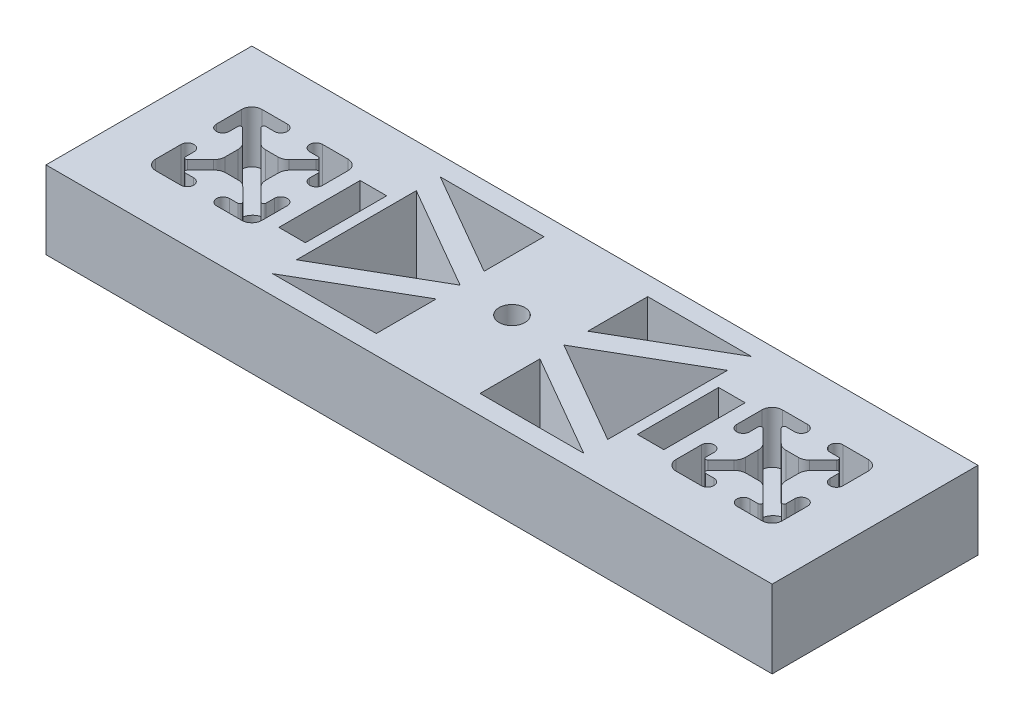
SolidWorks part; units mm, degrees
ref_plane "Front" through (0, 0, 0) normal (0, 0, 1) x (1, 0, 0)
ref_plane "Top" through (0, 0, 0) normal (0, 1, 0) x (1, 0, 0)
ref_plane "Right" through (0, 0, 0) normal (1, 0, 0) x (0, 0, -1)
sketch "Sketch1" plane through (0, 0, 0) normal (0, 1, 0) x (1, 0, 0)
  line L1 (0, 0) -> (177.8, 0)
  line L2 (0, 0) -> (0, 50.4)
  line L3 (0, 50.4) -> (177.8, 50.4)
  line L4 (177.8, 0) -> (177.8, 50.4)
  dimension "D1" = 177.8
  dimension "D2" = 50.4
extrude "Boss-Extrude1" add sketch "Sketch1" along normal blind 6.35
sketch "Sketch2" plane through (0, 6.35, 0) normal (0, 1, 0) x (1, 0, 0)
  line L0 (37.6996, 29.52) -> (37.6996, 35.7372) construction
  line L1 (35.7368, 37.7) -> (29.5196, 37.7) construction
  line L2 (29.5196, 35.56) -> (31.619, 35.56) construction
  line L3 (32.3326, 33.8353) -> (28.9966, 30.504) construction
  line L4 (26.7566, 29.5771) -> (23.643, 29.5771) construction
  line L5 (21.403, 30.504) -> (18.067, 33.8353) construction
  line L6 (18.7806, 35.56) -> (20.88, 35.56) construction
  line L7 (20.88, 37.7) -> (14.6628, 37.7) construction
  line L8 (12.7, 35.7372) -> (12.7, 29.52) construction
  line L9 (14.84, 29.52) -> (14.84, 31.5965) construction
  line L10 (16.5637, 32.3112) -> (19.7659, 29.1135) construction
  line L11 (20.743, 26.7568) -> (20.743, 23.6432) construction
  line L12 (19.7659, 21.2865) -> (16.5637, 18.0888) construction
  line L13 (14.84, 18.8035) -> (14.84, 20.88) construction
  line L14 (12.7, 20.88) -> (12.7, 14.6628) construction
  line L15 (14.6628, 12.7) -> (20.8121, 12.7) construction
  line L16 (20.8121, 14.84) -> (18.7806, 14.84) construction
  line L17 (18.067, 16.5647) -> (21.403, 19.896) construction
  line L18 (23.643, 20.8229) -> (26.7566, 20.8229) construction
  line L19 (28.9966, 19.896) -> (32.3326, 16.5647) construction
  line L20 (31.619, 14.84) -> (29.5875, 14.84) construction
  line L21 (29.5875, 12.7) -> (35.7368, 12.7) construction
  line L22 (37.6996, 14.6628) -> (37.6996, 20.88) construction
  line L23 (35.5596, 20.88) -> (35.5596, 18.8035) construction
  line L24 (33.8359, 18.0888) -> (30.6337, 21.2865) construction
  line L25 (29.6566, 23.6432) -> (29.6566, 26.7568) construction
  line L26 (30.6337, 29.1135) -> (33.8359, 32.3112) construction
  line L27 (35.5596, 31.5965) -> (35.5596, 29.52) construction
  line L28 (0, 50.4) -> (0, 0) construction
  line L29 (177.8, 50.4) -> (0, 50.4) construction
  line L30 (0, 0) -> (177.8, 0) construction
  line L31 (88.9, 50.4) -> (88.9, 0) construction
  line L32 (142.2404, 31.5965) -> (142.2404, 29.52) construction
  line L33 (147.1663, 29.1135) -> (143.9641, 32.3112) construction
  line L34 (148.1434, 23.6432) -> (148.1434, 26.7568) construction
  line L35 (143.9641, 18.0888) -> (147.1663, 21.2865) construction
  line L36 (142.2404, 20.88) -> (142.2404, 18.8035) construction
  line L37 (140.1004, 14.6628) -> (140.1004, 20.88) construction
  line L38 (148.2125, 12.7) -> (142.0632, 12.7) construction
  line L39 (146.181, 14.84) -> (148.2125, 14.84) construction
  line L40 (148.8034, 19.896) -> (145.4674, 16.5647) construction
  line L41 (154.157, 20.8229) -> (151.0434, 20.8229) construction
  line L42 (159.733, 16.5647) -> (156.397, 19.896) construction
  line L43 (156.9879, 14.84) -> (159.0194, 14.84) construction
  line L44 (163.1372, 12.7) -> (156.9879, 12.7) construction
  line L45 (165.1, 20.88) -> (165.1, 14.6628) construction
  line L46 (162.96, 18.8035) -> (162.96, 20.88) construction
  line L47 (158.0341, 21.2865) -> (161.2363, 18.0888) construction
  line L48 (157.057, 26.7568) -> (157.057, 23.6432) construction
  line L49 (161.2363, 32.3112) -> (158.0341, 29.1135) construction
  line L50 (162.96, 29.52) -> (162.96, 31.5965) construction
  line L51 (165.1, 35.7372) -> (165.1, 29.52) construction
  line L52 (156.92, 37.7) -> (163.1372, 37.7) construction
  line L53 (159.0194, 35.56) -> (156.92, 35.56) construction
  line L54 (156.397, 30.504) -> (159.733, 33.8353) construction
  line L55 (151.0434, 29.5771) -> (154.157, 29.5771) construction
  line L56 (145.4674, 33.8353) -> (148.8034, 30.504) construction
  line L57 (148.2804, 35.56) -> (146.181, 35.56) construction
  line L58 (142.0632, 37.7) -> (148.2804, 37.7) construction
  line L59 (140.1004, 29.52) -> (140.1004, 35.7372) construction
  line L60 (38.2076, 29.52) -> (38.2076, 35.7372)
  line L62 (0, 50.4) -> (0, 0)
  line L63 (0, 0) -> (177.8, 0)
  line L64 (177.8, 50.4) -> (177.8, 0)
  line L65 (35.7368, 38.208) -> (29.5196, 38.208)
  line L66 (29.5196, 35.052) -> (31.619, 35.052)
  line L67 (31.9737, 34.1948) -> (28.6376, 30.8635)
  line L68 (26.7566, 30.0851) -> (23.643, 30.0851)
  line L69 (21.762, 30.8635) -> (18.4259, 34.1948)
  line L70 (18.7806, 35.052) -> (20.88, 35.052)
  line L71 (20.88, 38.208) -> (14.6628, 38.208)
  line L72 (12.192, 35.7372) -> (12.192, 29.52)
  line L73 (15.348, 29.52) -> (15.348, 31.5965)
  line L74 (16.2047, 31.9517) -> (19.4069, 28.7541)
  line L75 (20.235, 26.7568) -> (20.235, 23.6432)
  line L76 (19.4069, 21.6459) -> (16.2047, 18.4483)
  line L77 (15.348, 18.8035) -> (15.348, 20.88)
  line L78 (12.192, 20.88) -> (12.192, 14.6628)
  line L79 (14.6628, 12.192) -> (20.8121, 12.192)
  line L80 (20.8121, 15.348) -> (18.7806, 15.348)
  line L81 (18.4259, 16.2052) -> (21.762, 19.5365)
  line L82 (23.643, 20.3149) -> (26.7566, 20.3149)
  line L83 (28.6376, 19.5365) -> (31.9737, 16.2052)
  line L84 (31.619, 15.348) -> (29.5875, 15.348)
  line L85 (29.5875, 12.192) -> (35.7368, 12.192)
  line L86 (38.2076, 14.6628) -> (38.2076, 20.88)
  line L87 (35.0516, 20.88) -> (35.0516, 18.8035)
  line L88 (34.1949, 18.4483) -> (30.9927, 21.6459)
  line L89 (30.1646, 23.6432) -> (30.1646, 26.7568)
  line L90 (30.9927, 28.7541) -> (34.1949, 31.9517)
  line L91 (35.0516, 31.5965) -> (35.0516, 29.52)
  line L92 (142.7484, 31.5965) -> (142.7484, 29.52)
  line L93 (139.5924, 29.52) -> (139.5924, 35.7372)
  line L94 (142.0632, 38.208) -> (148.2804, 38.208)
  line L95 (148.2804, 35.052) -> (146.181, 35.052)
  line L96 (145.8263, 34.1948) -> (149.1624, 30.8635)
  line L97 (151.0434, 30.0851) -> (154.157, 30.0851)
  line L98 (156.038, 30.8635) -> (159.3741, 34.1948)
  line L99 (159.0194, 35.052) -> (156.92, 35.052)
  line L100 (156.92, 38.208) -> (163.1372, 38.208)
  line L101 (165.608, 35.7372) -> (165.608, 29.52)
  line L102 (162.452, 29.52) -> (162.452, 31.5965)
  line L103 (161.5953, 31.9517) -> (158.3931, 28.7541)
  line L104 (157.565, 26.7568) -> (157.565, 23.6432)
  line L105 (158.3931, 21.6459) -> (161.5953, 18.4483)
  line L106 (162.452, 18.8035) -> (162.452, 20.88)
  line L107 (165.608, 20.88) -> (165.608, 14.6628)
  line L108 (163.1372, 12.192) -> (156.9879, 12.192)
  line L109 (156.9879, 15.348) -> (159.0194, 15.348)
  line L110 (159.3741, 16.2052) -> (156.038, 19.5365)
  line L111 (154.157, 20.3149) -> (151.0434, 20.3149)
  line L112 (149.1624, 19.5365) -> (145.8263, 16.2052)
  line L113 (146.181, 15.348) -> (148.2125, 15.348)
  line L114 (148.2125, 12.192) -> (142.0632, 12.192)
  line L115 (139.5924, 14.6628) -> (139.5924, 20.88)
  line L116 (142.7484, 20.88) -> (142.7484, 18.8035)
  line L117 (143.6051, 18.4483) -> (146.8073, 21.6459)
  line L118 (147.6354, 23.6432) -> (147.6354, 26.7568)
  line L119 (146.8073, 28.7541) -> (143.6051, 31.9517)
  line L120 (177.8, 50.4) -> (0, 50.4)
  arc A1 (37.6996, 35.7372) -> (35.7368, 37.7) centre (35.7368, 35.7372) ccw construction
  arc A2 (29.5196, 37.7) -> (29.5196, 35.56) centre (29.5196, 36.63) ccw construction
  arc A3 (31.619, 35.56) -> (32.3326, 33.8353) centre (31.619, 34.55) cw construction
  arc A4 (28.9966, 30.504) -> (26.7566, 29.5771) centre (26.7566, 32.7471) cw construction
  arc A5 (23.643, 29.5771) -> (21.403, 30.504) centre (23.643, 32.7471) cw construction
  arc A6 (18.067, 33.8353) -> (18.7806, 35.56) centre (18.7806, 34.55) cw construction
  arc A7 (20.88, 35.56) -> (20.88, 37.7) centre (20.88, 36.63) ccw construction
  arc A8 (14.6628, 37.7) -> (12.7, 35.7372) centre (14.6628, 35.7372) ccw construction
  arc A9 (12.7, 29.52) -> (14.84, 29.52) centre (13.77, 29.52) ccw construction
  arc A10 (14.84, 31.5965) -> (16.5637, 32.3112) centre (15.85, 31.5965) cw construction
  arc A11 (19.7659, 29.1135) -> (20.743, 26.7568) centre (17.4126, 26.7568) cw construction
  arc A12 (20.743, 23.6432) -> (19.7659, 21.2865) centre (17.4126, 23.6432) cw construction
  arc A13 (16.5637, 18.0888) -> (14.84, 18.8035) centre (15.85, 18.8035) cw construction
  arc A14 (14.84, 20.88) -> (12.7, 20.88) centre (13.77, 20.88) ccw construction
  arc A15 (12.7, 14.6628) -> (14.6628, 12.7) centre (14.6628, 14.6628) ccw construction
  arc A16 (20.8121, 12.7) -> (20.8121, 14.84) centre (20.8121, 13.77) ccw construction
  arc A17 (18.7806, 14.84) -> (18.067, 16.5647) centre (18.7806, 15.85) cw construction
  arc A18 (21.403, 19.896) -> (23.643, 20.8229) centre (23.643, 17.6529) cw construction
  arc A19 (26.7566, 20.8229) -> (28.9966, 19.896) centre (26.7566, 17.6529) cw construction
  arc A20 (32.3326, 16.5647) -> (31.619, 14.84) centre (31.619, 15.85) cw construction
  arc A21 (29.5875, 14.84) -> (29.5875, 12.7) centre (29.5875, 13.77) ccw construction
  arc A22 (35.7368, 12.7) -> (37.6996, 14.6628) centre (35.7368, 14.6628) ccw construction
  arc A23 (37.6996, 20.88) -> (35.5596, 20.88) centre (36.6296, 20.88) ccw construction
  arc A24 (35.5596, 18.8035) -> (33.8359, 18.0888) centre (34.5496, 18.8035) cw construction
  arc A25 (30.6337, 21.2865) -> (29.6566, 23.6432) centre (32.987, 23.6432) cw construction
  arc A26 (29.6566, 26.7568) -> (30.6337, 29.1135) centre (32.987, 26.7568) cw construction
  arc A27 (33.8359, 32.3112) -> (35.5596, 31.5965) centre (34.5496, 31.5965) cw construction
  arc A28 (35.5596, 29.52) -> (37.6996, 29.52) centre (36.6296, 29.52) ccw construction
  arc A29 (142.2404, 29.52) -> (140.1004, 29.52) centre (141.1704, 29.52) cw construction
  arc A30 (143.9641, 32.3112) -> (142.2404, 31.5965) centre (143.2504, 31.5965) ccw construction
  arc A31 (148.1434, 26.7568) -> (147.1663, 29.1135) centre (144.813, 26.7568) ccw construction
  arc A32 (147.1663, 21.2865) -> (148.1434, 23.6432) centre (144.813, 23.6432) ccw construction
  arc A33 (142.2404, 18.8035) -> (143.9641, 18.0888) centre (143.2504, 18.8035) ccw construction
  arc A34 (140.1004, 20.88) -> (142.2404, 20.88) centre (141.1704, 20.88) cw construction
  arc A35 (142.0632, 12.7) -> (140.1004, 14.6628) centre (142.0632, 14.6628) cw construction
  arc A36 (148.2125, 14.84) -> (148.2125, 12.7) centre (148.2125, 13.77) cw construction
  arc A37 (145.4674, 16.5647) -> (146.181, 14.84) centre (146.181, 15.85) ccw construction
  arc A38 (151.0434, 20.8229) -> (148.8034, 19.896) centre (151.0434, 17.6529) ccw construction
  arc A39 (156.397, 19.896) -> (154.157, 20.8229) centre (154.157, 17.6529) ccw construction
  arc A40 (159.0194, 14.84) -> (159.733, 16.5647) centre (159.0194, 15.85) ccw construction
  arc A41 (156.9879, 12.7) -> (156.9879, 14.84) centre (156.9879, 13.77) cw construction
  arc A42 (165.1, 14.6628) -> (163.1372, 12.7) centre (163.1372, 14.6628) cw construction
  arc A43 (162.96, 20.88) -> (165.1, 20.88) centre (164.03, 20.88) cw construction
  arc A44 (161.2363, 18.0888) -> (162.96, 18.8035) centre (161.95, 18.8035) ccw construction
  arc A45 (157.057, 23.6432) -> (158.0341, 21.2865) centre (160.3874, 23.6432) ccw construction
  arc A46 (158.0341, 29.1135) -> (157.057, 26.7568) centre (160.3874, 26.7568) ccw construction
  arc A47 (162.96, 31.5965) -> (161.2363, 32.3112) centre (161.95, 31.5965) ccw construction
  arc A48 (165.1, 29.52) -> (162.96, 29.52) centre (164.03, 29.52) cw construction
  arc A49 (163.1372, 37.7) -> (165.1, 35.7372) centre (163.1372, 35.7372) cw construction
  arc A50 (156.92, 35.56) -> (156.92, 37.7) centre (156.92, 36.63) cw construction
  arc A51 (159.733, 33.8353) -> (159.0194, 35.56) centre (159.0194, 34.55) ccw construction
  arc A52 (154.157, 29.5771) -> (156.397, 30.504) centre (154.157, 32.7471) ccw construction
  arc A53 (148.8034, 30.504) -> (151.0434, 29.5771) centre (151.0434, 32.7471) ccw construction
  arc A54 (146.181, 35.56) -> (145.4674, 33.8353) centre (146.181, 34.55) ccw construction
  arc A55 (148.2804, 37.7) -> (148.2804, 35.56) centre (148.2804, 36.63) cw construction
  arc A56 (140.1004, 35.7372) -> (142.0632, 37.7) centre (142.0632, 35.7372) cw construction
  arc A58 (38.2076, 35.7372) -> (35.7368, 38.208) centre (35.7368, 35.7372) ccw
  arc A59 (29.5196, 38.208) -> (29.5196, 35.052) centre (29.5196, 36.63) ccw
  arc A60 (31.619, 35.052) -> (31.9737, 34.1948) centre (31.619, 34.55) cw
  arc A61 (28.6376, 30.8635) -> (26.7566, 30.0851) centre (26.7566, 32.7471) cw
  arc A62 (23.643, 30.0851) -> (21.762, 30.8635) centre (23.643, 32.7471) cw
  arc A63 (18.4259, 34.1948) -> (18.7806, 35.052) centre (18.7806, 34.55) cw
  arc A64 (20.88, 35.052) -> (20.88, 38.208) centre (20.88, 36.63) ccw
  arc A65 (14.6628, 38.208) -> (12.192, 35.7372) centre (14.6628, 35.7372) ccw
  arc A66 (12.192, 29.52) -> (15.348, 29.52) centre (13.77, 29.52) ccw
  arc A67 (15.348, 31.5965) -> (16.2047, 31.9517) centre (15.85, 31.5965) cw
  arc A68 (19.4069, 28.7541) -> (20.235, 26.7568) centre (17.4126, 26.7568) cw
  arc A69 (20.235, 23.6432) -> (19.4069, 21.6459) centre (17.4126, 23.6432) cw
  arc A70 (16.2047, 18.4483) -> (15.348, 18.8035) centre (15.85, 18.8035) cw
  arc A71 (15.348, 20.88) -> (12.192, 20.88) centre (13.77, 20.88) ccw
  arc A72 (12.192, 14.6628) -> (14.6628, 12.192) centre (14.6628, 14.6628) ccw
  arc A73 (20.8121, 12.192) -> (20.8121, 15.348) centre (20.8121, 13.77) ccw
  arc A74 (18.7806, 15.348) -> (18.4259, 16.2052) centre (18.7806, 15.85) cw
  arc A75 (21.762, 19.5365) -> (23.643, 20.3149) centre (23.643, 17.6529) cw
  arc A76 (26.7566, 20.3149) -> (28.6376, 19.5365) centre (26.7566, 17.6529) cw
  arc A77 (31.9737, 16.2052) -> (31.619, 15.348) centre (31.619, 15.85) cw
  arc A78 (29.5875, 15.348) -> (29.5875, 12.192) centre (29.5875, 13.77) ccw
  arc A79 (35.7368, 12.192) -> (38.2076, 14.6628) centre (35.7368, 14.6628) ccw
  arc A80 (38.2076, 20.88) -> (35.0516, 20.88) centre (36.6296, 20.88) ccw
  arc A81 (35.0516, 18.8035) -> (34.1949, 18.4483) centre (34.5496, 18.8035) cw
  arc A82 (30.9927, 21.6459) -> (30.1646, 23.6432) centre (32.987, 23.6432) cw
  arc A83 (30.1646, 26.7568) -> (30.9927, 28.7541) centre (32.987, 26.7568) cw
  arc A84 (34.1949, 31.9517) -> (35.0516, 31.5965) centre (34.5496, 31.5965) cw
  arc A85 (35.0516, 29.52) -> (38.2076, 29.52) centre (36.6296, 29.52) ccw
  arc A86 (142.7484, 29.52) -> (139.5924, 29.52) centre (141.1704, 29.52) cw
  arc A87 (139.5924, 35.7372) -> (142.0632, 38.208) centre (142.0632, 35.7372) cw
  arc A88 (148.2804, 38.208) -> (148.2804, 35.052) centre (148.2804, 36.63) cw
  arc A89 (146.181, 35.052) -> (145.8263, 34.1948) centre (146.181, 34.55) ccw
  arc A90 (149.1624, 30.8635) -> (151.0434, 30.0851) centre (151.0434, 32.7471) ccw
  arc A91 (154.157, 30.0851) -> (156.038, 30.8635) centre (154.157, 32.7471) ccw
  arc A92 (159.3741, 34.1948) -> (159.0194, 35.052) centre (159.0194, 34.55) ccw
  arc A93 (156.92, 35.052) -> (156.92, 38.208) centre (156.92, 36.63) cw
  arc A94 (163.1372, 38.208) -> (165.608, 35.7372) centre (163.1372, 35.7372) cw
  arc A95 (165.608, 29.52) -> (162.452, 29.52) centre (164.03, 29.52) cw
  arc A96 (162.452, 31.5965) -> (161.5953, 31.9517) centre (161.95, 31.5965) ccw
  arc A97 (158.3931, 28.7541) -> (157.565, 26.7568) centre (160.3874, 26.7568) ccw
  arc A98 (157.565, 23.6432) -> (158.3931, 21.6459) centre (160.3874, 23.6432) ccw
  arc A99 (161.5953, 18.4483) -> (162.452, 18.8035) centre (161.95, 18.8035) ccw
  arc A100 (162.452, 20.88) -> (165.608, 20.88) centre (164.03, 20.88) cw
  arc A101 (165.608, 14.6628) -> (163.1372, 12.192) centre (163.1372, 14.6628) cw
  arc A102 (156.9879, 12.192) -> (156.9879, 15.348) centre (156.9879, 13.77) cw
  arc A103 (159.0194, 15.348) -> (159.3741, 16.2052) centre (159.0194, 15.85) ccw
  arc A104 (156.038, 19.5365) -> (154.157, 20.3149) centre (154.157, 17.6529) ccw
  arc A105 (151.0434, 20.3149) -> (149.1624, 19.5365) centre (151.0434, 17.6529) ccw
  arc A106 (145.8263, 16.2052) -> (146.181, 15.348) centre (146.181, 15.85) ccw
  arc A107 (148.2125, 15.348) -> (148.2125, 12.192) centre (148.2125, 13.77) cw
  arc A108 (142.0632, 12.192) -> (139.5924, 14.6628) centre (142.0632, 14.6628) cw
  arc A109 (139.5924, 20.88) -> (142.7484, 20.88) centre (141.1704, 20.88) cw
  arc A110 (142.7484, 18.8035) -> (143.6051, 18.4483) centre (143.2504, 18.8035) ccw
  arc A111 (146.8073, 21.6459) -> (147.6354, 23.6432) centre (144.813, 23.6432) ccw
  arc A112 (147.6354, 26.7568) -> (146.8073, 28.7541) centre (144.813, 26.7568) ccw
  arc A113 (143.6051, 31.9517) -> (142.7484, 31.5965) centre (143.2504, 31.5965) ccw
  dimension "D2" = 1.07
  dimension "D3" = 3.17
  dimension "D4" = 3.3305
  dimension "D8" = 1.9628
  dimension "D9" = 1.01
  dimension "D5" = 12.7
  dimension "D6" = 12.7
  dimension "D7" = 12.7
  dimension "D10" = 16.5637
  dimension "D12" = 0.508
  dimension "D13" = 0.508
extrude "Boss-Extrude2" add sketch "Sketch2" along normal blind 12.7
sketch "Sketch3" plane through (0, 19.05, 0) normal (0, 1, 0) x (1, 0, 0)
  line L0 (177.8, 50.4) -> (0, 50.4) construction
  line L1 (0, 50.4) -> (0, 0) construction
  circle A0 centre (88.9, 25.2) radius 3.175
  point P4 (88.9, 50.4)
  point P7 (0, 25.2)
  dimension "D1" = 6.35
extrude "Cut-Extrude1" cut sketch "Sketch3" against normal blind 10.16
sketch "Sketch4" plane through (0, 19.05, 0) normal (0, 1, 0) x (1, 0, 0)
  line L0 (50.8, 45.7306) -> (76.2, 45.7306)
  line L1 (76.2, 45.7306) -> (76.2, 31.0659)
  line L2 (76.2, 31.0659) -> (50.8, 45.7306)
  line L3 (76.2, 19.3341) -> (76.2, 4.6694)
  line L4 (76.2, 4.6694) -> (50.8, 4.6694)
  line L5 (50.8, 4.6694) -> (76.2, 19.3341)
  line L6 (50.8, 39.8647) -> (50.8, 10.5353)
  line L7 (50.8, 10.5353) -> (76.2, 25.2)
  line L8 (76.2, 25.2) -> (50.8, 39.8647)
  line L9 (0, 50.4) -> (0, 0) construction
  line L10 (88.9, 50.4) -> (88.9, 0) construction
  line L11 (177.8, 50.4) -> (0, 50.4) construction
  line L12 (0, 0) -> (177.8, 0) construction
  line L13 (101.6, 25.2) -> (127, 39.8647)
  line L14 (127, 10.5353) -> (101.6, 25.2)
  line L15 (127, 39.8647) -> (127, 10.5353)
  line L16 (127, 4.6694) -> (101.6, 19.3341)
  line L17 (101.6, 4.6694) -> (127, 4.6694)
  line L18 (101.6, 19.3341) -> (101.6, 4.6694)
  line L19 (101.6, 31.0659) -> (127, 45.7306)
  line L20 (101.6, 45.7306) -> (101.6, 31.0659)
  line L21 (127, 45.7306) -> (101.6, 45.7306)
  point P18 (88.9, 25.2)
  dimension "D1" = 25.4
  dimension "D2" = 25.4
  dimension "D3" = 50.8
  dimension "D4" = 5.08
  dimension "D5" = 5.08
  dimension "D7" = 60
extrude "Cut-Extrude2" cut sketch "Sketch4" against normal through all
sketch "Sketch5" plane through (0, 19.05, 0) normal (0, 1, 0) x (1, 0, 0)
  line L0 (0, 50.4) -> (0, 0) construction
  line L1 (41.7636, 35.15) -> (48.2636, 35.15)
  line L2 (41.7636, 35.15) -> (41.7636, 15.25)
  line L3 (41.7636, 15.25) -> (48.2636, 15.25)
  line L4 (48.2636, 35.15) -> (48.2636, 15.25)
  line L5 (38.2076, 29.52) -> (38.2076, 35.7372) construction
  point P6 (0, 25.2)
  point P7 (48.2636, 25.2)
  dimension "D1" = 6.5
  dimension "D2" = 19.9
  dimension "D3" = 3.556
extrude "Cut-Extrude3" cut sketch "Sketch5" against normal blind 10.2
sketch "Sketch6" plane through (0, 8.85, 0) normal (0, 1, 0) x (1, 0, 0)
  line L0 (48.2636, 15.25) -> (48.2636, 35.15) construction
  line L1 (41.7636, 35.15) -> (48.2636, 35.15)
  line L2 (41.7636, 35.15) -> (41.7636, 30.578)
  line L3 (41.7636, 30.578) -> (48.2636, 30.578)
  line L4 (48.2636, 35.15) -> (48.2636, 30.578)
  line L5 (41.7636, 35.15) -> (41.7636, 15.25) construction
  line L6 (48.2636, 15.25) -> (48.2636, 35.15) construction
  line L7 (41.7636, 27.486) -> (48.2636, 27.486)
  line L8 (41.7636, 27.486) -> (41.7636, 22.914)
  line L9 (41.7636, 22.914) -> (48.2636, 22.914)
  line L10 (48.2636, 27.486) -> (48.2636, 22.914)
  line L12 (41.7636, 15.25) -> (48.2636, 15.25)
  line L13 (41.7636, 15.25) -> (41.7636, 19.822)
  line L14 (41.7636, 19.822) -> (48.2636, 19.822)
  line L15 (48.2636, 15.25) -> (48.2636, 19.822)
  line L16 (41.7636, 25.2) -> (0, 25.2) construction
  line L17 (0, 50.4) -> (0, 0) construction
  dimension "D1" = 4.572
extrude "Cut-Extrude4" cut sketch "Sketch6" against normal through all
ref_plane "Plane1" through (88.9, 0, 0) normal (-1, 0, 0) x (0, 0, 1)
mirror "Mirror1" about plane through (88.9, 0, 0) normal (-1, 0, 0) of "Cut-Extrude4", "Cut-Extrude3"
sketch "Sketch7" plane through (0, 6.35, 0) normal (0, 1, 0) x (1, 0, 0)
  line L0 (26.7566, 30.0851) -> (23.643, 30.0851) construction
  line L1 (30.1646, 23.6432) -> (30.1646, 26.7568) construction
  circle A0 centre (25.3386, 25.2591) radius 2.921
  point P6 (0, 0)
  dimension "D1" = 5.842
  dimension "D2" = 4.826
  dimension "D3" = 4.826
extrude "Cut-Extrude5" cut sketch "Sketch7" against normal through all both and the other way through all
sketch "Sketch8" plane through (0, 6.35, 0) normal (0, 1, 0) x (1, 0, 0)
  line L0 (154.157, 30.0851) -> (151.0434, 30.0851) construction
  line L1 (157.565, 23.6432) -> (157.565, 26.7568) construction
  circle A0 centre (152.739, 25.2591) radius 2.921
  dimension "D1" = 5.842
  dimension "D2" = 4.826
  dimension "D3" = 4.826
extrude "Cut-Extrude6" cut sketch "Sketch8" against normal through all both and the other way through all
chamfer "Chamfer2" distance 3.302 angle 45 1 edges at (152.739, 0, -22.3381)
chamfer "Chamfer3" distance 3.302 angle 45 1 edges at (25.3386, 0, -22.3381)
